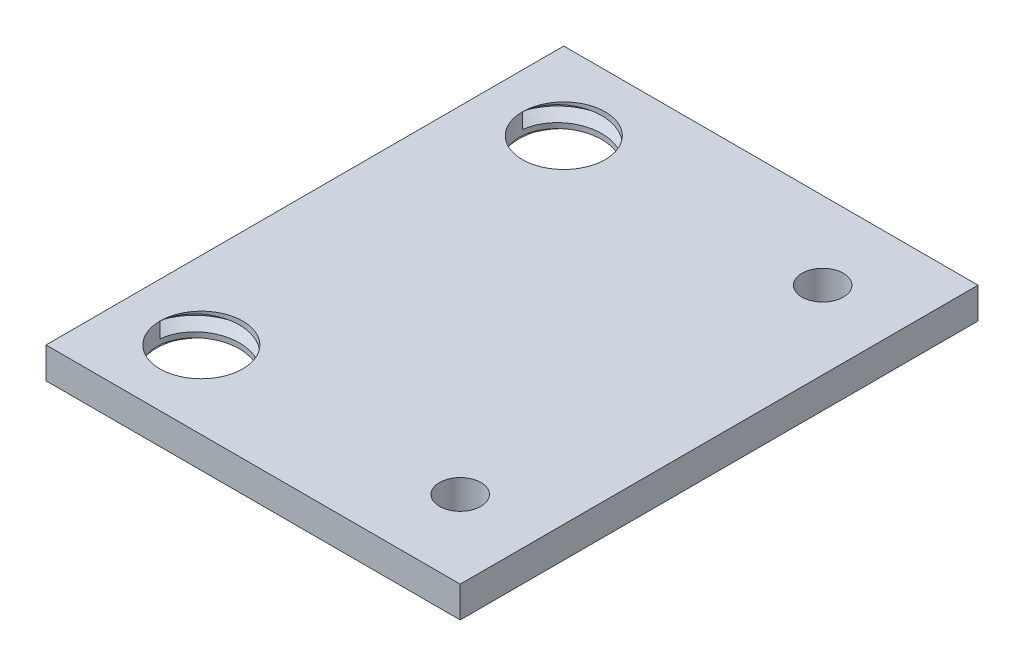
SolidWorks part; units mm, degrees
ref_plane "Front Plane" through (0, 0, 0) normal (0, 0, 1) x (1, 0, 0)
ref_plane "Top Plane" through (0, 0, 0) normal (0, 1, 0) x (1, 0, 0)
ref_plane "Right Plane" through (0, 0, 0) normal (1, 0, 0) x (0, 0, -1)
sketch "Sketch1" plane through (0, 0, 0) normal (0, 1, 0) x (1, 0, 0)
  line L1 (-88.0961, 3.7304) -> (-48.0961, 3.7304)
  line L2 (-88.0961, 3.7304) -> (-88.0961, -46.2696)
  line L3 (-88.0961, -46.2696) -> (-48.0961, -46.2696)
  line L4 (-48.0961, 3.7304) -> (-48.0961, -46.2696)
  line L5 (-88.0961, -21.2696) -> (-48.0961, -21.2696) construction
  line L11 (-68.0961, 3.7304) -> (-68.0961, -46.2696) construction
  circle A4 centre (-55.5961, -3.7696) radius 2
  circle A5 centre (-55.5961, -38.7696) radius 2
  circle A6 centre (-55.5961, -3.7696) radius 2 construction
  circle A7 centre (-80.5961, -38.7696) radius 4
  circle A9 centre (-80.5961, -3.7696) radius 4
  dimension "D3" = 7.5
  dimension "D5" = 4
  dimension "D6" = 8
  dimension "D1" = 50
  dimension "D2" = 40
  dimension "D4" = 7.5
extrude "Boss-Extrude1" add sketch "Sketch1" along normal blind 3
thread "Thread1" pitch 2 method cut profile "Thread Profile1" start angle 0, offset 0, length 3, pitch 2, diameter 8
ref_plane "Plane1" through (-84.5961, 3, 3.7696) normal (0, 0, 1) x (-1, 0, 0)
sketch "Thread Profile1" plane through (-84.5961, 3, 3.7696) normal (0, 0, 1) x (-1, 0, 0)
  line L0 (0, 0) -> (0, 2) construction
  line L1 (0, 0) -> (1.0825, 0.625)
  line L2 (1.0825, 0.625) -> (1.0825, 0.875)
  line L3 (1.0825, 0.875) -> (0, 1.5)
  line L4 (1.0825, 0.75) -> (0, 0.75) construction
  line L11 (0, 0) -> (0, 1.5)
  point P2 (0, 0)
  dimension "Pitch" = 2
  dimension "Profile_Angle" = 60
  dimension "Profile_Land" = 0.25
  dimension "Profile_Height" = 1.0825
thread "Thread2" pitch 2 method cut profile "Thread Profile2" start angle 0, offset 0, length 3, pitch 2, diameter 8
ref_plane "Plane2" through (-84.5961, 3, 38.7696) normal (0, 0, 1) x (-1, 0, 0)
sketch "Thread Profile2" plane through (-84.5961, 3, 38.7696) normal (0, 0, 1) x (-1, 0, 0)
  line L0 (0, 0) -> (0, 2) construction
  line L1 (0, 0) -> (1.0825, 0.625)
  line L2 (1.0825, 0.625) -> (1.0825, 0.875)
  line L3 (1.0825, 0.875) -> (0, 1.5)
  line L4 (1.0825, 0.75) -> (0, 0.75) construction
  line L11 (0, 0) -> (0, 1.5)
  point P2 (0, 0)
  dimension "Pitch" = 2
  dimension "Profile_Angle" = 60
  dimension "Profile_Land" = 0.25
  dimension "Profile_Height" = 1.0825
